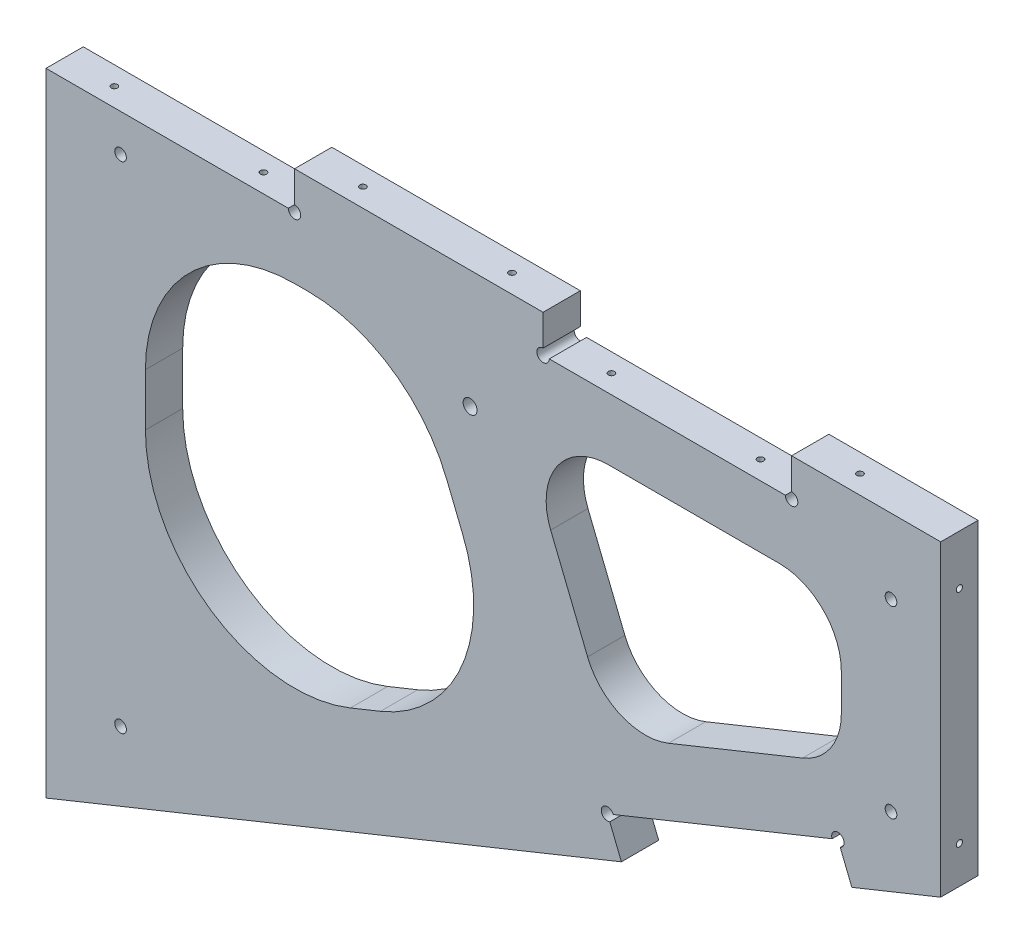
SolidWorks part; units mm, degrees
material "Beech"
ref_plane "Front Plane" through (0, 0, 0) normal (0, 0, 1) x (1, 0, 0)
ref_plane "Top Plane" through (0, 0, 0) normal (0, 1, 0) x (1, 0, 0)
ref_plane "Right Plane" through (0, 0, 0) normal (1, 0, 0) x (0, 0, -1)
sketch "Sketch1" plane through (0, 0, 0) normal (0, 0, 1) x (1, 0, 0)
  line L0 (3140.71, 6983.73) -> (2683.51, 6983.73)
  line L1 (3140.71, 6826.4627) -> (3140.71, 6983.73) construction
  line L2 (3140.71, 6983.73) -> (2683.51, 6983.73) construction
  line L3 (2683.51, 6983.73) -> (2683.51, 6641.7419)
  line L4 (2683.51, 6641.7419) -> (3140.71, 6826.4627)
  line L5 (3140.71, 6826.4627) -> (3140.71, 6983.73)
extrude "Boss-Extrude1" add sketch "Sketch1" along normal blind 19.05
sketch "Sketch6" plane through (0, 0, 0) normal (0, 0, -1) x (-1, 0, 0)
  line L0 (-2925.0567, 6794.1227) -> (-2872.8192, 6923.415) construction
  line L1 (-2923.7645, 6932.93) -> (-3089.91, 6932.93)
  line L2 (-2925.0567, 6794.1227) -> (-2734.31, 6717.056)
  line L4 (-2948.6072, 6803.6377) -> (-2896.3697, 6932.93) construction
  line L5 (-2925.0567, 6794.1227) -> (-2868.9749, 6932.93)
  line L6 (-2972.1577, 6813.1527) -> (-2923.7645, 6932.93)
  line L7 (-2972.1577, 6813.1527) -> (-2919.9202, 6942.445) construction
  line L8 (-3089.91, 6932.93) -> (-3089.91, 6860.7277)
  line L9 (-3089.91, 6860.7277) -> (-2734.31, 6717.056)
  line L10 (-2734.31, 6717.056) -> (-2734.31, 6932.93)
  line L11 (-2734.31, 6932.93) -> (-3089.91, 6932.93)
  line L12 (-3089.91, 6932.93) -> (-3089.91, 6860.7277)
  line L13 (-3089.91, 6860.7277) -> (-2972.1577, 6813.1527)
  line L14 (-2734.31, 6717.056) -> (-2734.31, 6932.93)
  line L15 (-2734.31, 6932.93) -> (-2868.9749, 6932.93)
  dimension "D2" = 152.4
  dimension "D1" = 50.8
  dimension "D3" = 25.4
  dimension "D4" = 25.4
extrude "Cut-Extrude2" cut sketch "Sketch6" against normal through all
fillet "Fillet1" radius 76.2 4 edges at (2734.31, 6932.93, 9.525) (2868.9749, 6932.93, 9.525) (2925.0567, 6794.1227, 9.525) (2734.31, 6717.056, 9.525)
fillet "Fillet2" radius 31.75 4 edges at (3089.91, 6860.7277, 9.525) (2972.1577, 6813.1527, 9.525) (2923.7645, 6932.93, 9.525) (3089.91, 6932.93, 9.525)
sketch "Sketch2" plane through (0, 0, 0) normal (0, 0, -1) x (-1, 0, 0)
  line L0 (-2683.51, 6964.68) -> (-2810.51, 6964.68) construction
  line L1 (-2810.51, 6964.68) -> (-2810.51, 6983.73) construction
  line L2 (-2810.51, 6983.73) -> (-2683.51, 6983.73) construction
  line L3 (-2683.51, 6983.73) -> (-2683.51, 6964.68) construction
  line L4 (-2937.51, 6964.68) -> (-3064.51, 6964.68) construction
  line L5 (-3064.51, 6964.68) -> (-3064.51, 6983.73) construction
  line L6 (-3064.51, 6983.73) -> (-2937.51, 6983.73) construction
  line L7 (-2937.51, 6983.73) -> (-2937.51, 6964.68) construction
  line L8 (-2977.5519, 6760.5425) -> (-3095.3042, 6808.1176) construction
  line L9 (-3095.3042, 6808.1176) -> (-3088.168, 6825.7804) construction
  line L10 (-3088.168, 6825.7804) -> (-2970.4156, 6778.2054) construction
  line L11 (-2970.4156, 6778.2054) -> (-2977.5519, 6760.5425) construction
  line L12 (-2683.51, 6964.68) -> (-2810.51, 6964.68)
  line L13 (-2810.51, 6964.68) -> (-2810.51, 6983.73)
  line L14 (-2810.51, 6983.73) -> (-2683.51, 6983.73)
  line L15 (-2683.51, 6983.73) -> (-2683.51, 6964.68)
  line L16 (-2937.51, 6964.68) -> (-3064.51, 6964.68)
  line L17 (-3064.51, 6964.68) -> (-3064.51, 6983.73)
  line L18 (-3064.51, 6983.73) -> (-2937.51, 6983.73)
  line L19 (-2937.51, 6983.73) -> (-2937.51, 6964.68)
  line L20 (-2977.5519, 6760.5425) -> (-3095.3042, 6808.1176)
  line L21 (-3095.3042, 6808.1176) -> (-3088.168, 6825.7804)
  line L22 (-3088.168, 6825.7804) -> (-2970.4156, 6778.2054)
  line L23 (-2970.4156, 6778.2054) -> (-2977.5519, 6760.5425)
extrude "Cut-Extrude1" cut sketch "Sketch2" against normal through all
hole_wizard "1/4 (0.25) Diameter Hole1" positions "Sketch3" profile "Sketch4" hole size "1/4" standard "ANSI Inch" end condition through all
sketch "Sketch3" plane through (0, 0, 0) normal (0, 0, -1) x (-1, 0, 0)
  point P0 (-3088.168, 6825.7804)
  point P3 (-2970.4156, 6778.2054)
  point P6 (-2937.51, 6964.68)
  point P9 (-3064.51, 6964.68)
  point P12 (-2810.51, 6964.68)
sketch "Sketch4" plane through (3088.168, 6825.7804, 0) normal (1, 0, 0) x (0, 1, 0)
  line L0 (0, 0) -> (0, 19.05)
  line L1 (0, 19.05) -> (3.175, 19.05)
  line L2 (3.175, 19.05) -> (3.175, 0)
  line L5 (3.175, 0) -> (0, 0)
  line L11 (0, -6.35) -> (0, 107.95) construction
  dimension "Thru Hole Dia." = 6.35
  dimension "Thru Hole Depth" = 19.05
hole_wizard "15/64 (0.23438) Diameter Hole1" positions "Sketch7" profile "Sketch8" hole size "15/64" standard "ANSI Inch" end condition through all
sketch "Sketch7" plane through (0, 0, 0) normal (0, 0, -1) x (0, 1, 0)
  point P0 (6692.5419, 2721.61)
  point P1 (6945.63, 2721.61)
  point P2 (6945.63, 3115.31)
  point P3 (6851.607, 3115.31)
sketch "Sketch8" plane through (2721.61, 6692.5419, 0) normal (1, 0, 0) x (0, 1, 0)
  line L0 (0, 0) -> (0, 19.05)
  line L1 (0, 19.05) -> (2.9766, 19.05)
  line L2 (2.9766, 19.05) -> (2.9766, 0)
  line L3 (2.9766, 0) -> (0, 0)
  line L4 (0, -6.35) -> (0, 107.95) construction
  dimension "Thru Hole Dia." = 5.9533
  dimension "Thru Hole Depth" = 19.05
hole_wizard "1/4 Clearance Hole1" positions "Sketch9" profile "Sketch10" hole size "1/4" standard "ANSI Inch" end condition through all
sketch "Sketch9" plane through (0, 0, 0) normal (0, 0, -1) x (-1, 0, 0)
  point P0 (-2900.218, 6923.405)
sketch "Sketch10" plane through (2900.218, 6923.405, 0) normal (1, 0, 0) x (0, 1, 0)
  line L0 (0, 0) -> (0, 19.05)
  line L1 (0, 19.05) -> (3.5712, 19.05)
  line L2 (3.5712, 19.05) -> (3.5712, 0)
  line L5 (3.5712, 0) -> (0, 0)
  line L11 (0, -6.35) -> (0, 107.95) construction
  dimension "Thru Hole Dia." = 7.1425
  dimension "Thru Hole Depth" = 19.05
hole_wizard "Hole1" positions "Sketch11" profile "Sketch12" legacy
sketch "Sketch11" plane through (0, 7002.78, 247.523) normal (0, 1, 0) x (0, 0, 1)
  line L0 (-237.998, 3140.71) -> (-237.998, 2683.51) construction
  line L9 (0, 3140.71) -> (0, 2683.51) construction
  point P13 (-237.998, 3089.91)
  point P15 (-237.998, 3039.11)
  point P17 (-237.998, 2962.91)
  point P19 (-237.998, 2912.11)
  point P21 (-237.998, 2835.91)
  point P23 (-237.998, 2785.11)
  point P25 (-237.998, 2708.91)
  point P38 (237.998, 2708.91)
  point P39 (237.998, 2785.11)
  point P40 (237.998, 2835.91)
  point P41 (237.998, 2912.11)
  point P42 (237.998, 2962.91)
  point P43 (237.998, 3039.11)
  point P44 (237.998, 3089.91)
  point P50 (0, 3051.81)
  point P52 (0, 2950.21)
  point P54 (0, 2797.81)
  point P56 (0, 2696.21)
sketch "Sketch12" plane through (2696.21, 7002.78, 247.523) normal (1, 0, 0) x (0, 0, 1)
  line L0 (0, 0) -> (0, 51.7539)
  line L1 (0, 51.7539) -> (1.5875, 50.8)
  line L2 (1.5875, 50.8) -> (1.5875, 4.0177)
  line L3 (1.5875, 4.0177) -> (5.08, 0)
  line L4 (5.08, 0) -> (0, 0)
  line L5 (0, -14.3089) -> (0, 102.4216) construction
  line L6 (0, 51.7539) -> (-1.5875, 50.8) construction
  line L7 (-1.5875, 4.0177) -> (-5.08, 0) construction
  dimension "Diameter" = 3.175
  dimension "Depth" = 50.8
  dimension "C-Sink Diameter" = 10.16
  dimension "C-Sink Angle" = 82
  dimension "Drill Angle" = 118
hole_wizard "Hole2" positions "Sketch13" profile "Sketch14" legacy
sketch "Sketch13" plane through (3159.76, 0, 247.523) normal (1, 0, 0) x (0, 0, -1)
  line L0 (237.998, 6813.6133) -> (237.998, 7002.78) construction
  line L5 (0, 6813.6133) -> (0, 7002.78) construction
  line L7 (266.573, 6993.255) -> (-266.573, 6993.255) construction
  line L17 (237.998, 6845.5127) -> (237.998, 6958.33)
  line L18 (237.998, 6993.255) -> (0, 6993.255)
  point P30 (237.998, 6993.255)
  point P32 (237.998, 6958.33)
  point P34 (237.998, 6845.5127)
  point P50 (-237.998, 6993.255)
  point P51 (-237.998, 6958.33)
  point P52 (-237.998, 6845.5127)
  point P60 (118.999, 6993.255)
  point P64 (-118.999, 6993.255)
sketch "Sketch14" plane through (3159.76, 6993.255, 366.522) normal (0, 1, 0) x (0, 0, -1)
  line L0 (0, 0) -> (0, 39.0539)
  line L1 (0, 39.0539) -> (1.5875, 38.1)
  line L2 (1.5875, 38.1) -> (1.5875, 4.0177)
  line L3 (1.5875, 4.0177) -> (5.08, 0)
  line L4 (5.08, 0) -> (0, 0)
  line L5 (0, -14.3089) -> (0, 102.4216) construction
  line L6 (0, 39.0539) -> (-1.5875, 38.1) construction
  line L7 (-1.5875, 4.0177) -> (-5.08, 0) construction
  dimension "Diameter" = 3.175
  dimension "Depth" = 38.1
  dimension "C-Sink Diameter" = 10.16
  dimension "C-Sink Angle" = 82
  dimension "Drill Angle" = 118
hole_wizard "Hole3" positions "Sketch15" profile "Sketch16" legacy
sketch "Sketch15" plane through (-1923.1573, 4759.9814, 247.523) normal (0.3746, -0.9272, 0) x (0, 0, -1)
  line L0 (-237.998, 5461.5568) -> (-237.998, 4968.4508) construction
  line L6 (0, 5461.5568) -> (0, 5275.5865) construction
  line L10 (-237.998, 5267.8818) -> (-237.998, 4993.8508)
  point P19 (-237.998, 5442.5068)
  point P21 (-237.998, 5394.8818)
  point P23 (-237.998, 5318.6818)
  point P32 (0, 5407.5818)
  point P34 (0, 5305.9818)
  point P37 (-237.998, 5267.8818)
  point P39 (-237.998, 5130.8663)
  point P41 (-237.998, 4993.8508)
  point P64 (237.998, 4993.8508)
  point P65 (237.998, 5130.8663)
  point P66 (237.998, 5267.8818)
  point P67 (237.998, 5318.6818)
  point P68 (237.998, 5394.8818)
  point P69 (237.998, 5442.5068)
sketch "Sketch16" plane through (3123.0471, 6798.7803, 9.525) normal (0, 0, 1) x (0.9272, 0.3746, 0)
  line L0 (0, 0) -> (0, 51.7539)
  line L1 (0, 51.7539) -> (1.5875, 50.8)
  line L2 (1.5875, 50.8) -> (1.5875, 4.0177)
  line L3 (1.5875, 4.0177) -> (5.08, 0)
  line L4 (5.08, 0) -> (0, 0)
  line L5 (0, -14.3089) -> (0, 102.4216) construction
  line L6 (0, 51.7539) -> (-1.5875, 50.8) construction
  line L7 (-1.5875, 4.0177) -> (-5.08, 0) construction
  dimension "Diameter" = 3.175
  dimension "Depth" = 50.8
  dimension "C-Sink Diameter" = 10.16
  dimension "C-Sink Angle" = 82
  dimension "Drill Angle" = 118
hole_wizard "Hole4" positions "Sketch17" profile "Sketch18" legacy
sketch "Sketch17" plane through (2664.46, 0, 247.523) normal (-1, 0, 0) x (0, 0, 1)
  line L0 (0, 7002.78) -> (0, 5935.98) construction
  line L4 (237.998, 7002.78) -> (237.998, 5935.98) construction
  line L8 (266.573, 6993.255) -> (0, 6993.255) construction
  line L12 (237.998, 6939.28) -> (237.998, 6686.1919)
  point P26 (237.998, 6686.1919)
  point P27 (257.048, 6993.255)
  point P29 (218.948, 6993.255)
  point P31 (19.05, 6993.255)
  point P35 (237.998, 6939.28)
  point P42 (237.998, 6812.7359)
  point P51 (-237.998, 6812.7359)
  point P52 (-237.998, 6939.28)
  point P53 (-19.05, 6993.255)
  point P54 (-218.948, 6993.255)
  point P55 (-257.048, 6993.255)
  point P56 (-237.998, 6686.1919)
sketch "Sketch18" plane through (2664.46, 6686.1919, 9.525) normal (0, 1, 0) x (0, 0, 1)
  line L0 (0, 0) -> (0, 39.0539)
  line L1 (0, 39.0539) -> (1.5875, 38.1)
  line L2 (1.5875, 38.1) -> (1.5875, 4.0177)
  line L3 (1.5875, 4.0177) -> (5.08, 0)
  line L4 (5.08, 0) -> (0, 0)
  line L5 (0, -14.3089) -> (0, 102.4216) construction
  line L6 (0, 39.0539) -> (-1.5875, 38.1) construction
  line L7 (-1.5875, 4.0177) -> (-5.08, 0) construction
  dimension "Diameter" = 3.175
  dimension "Depth" = 38.1
  dimension "C-Sink Diameter" = 10.16
  dimension "C-Sink Angle" = 82
  dimension "Drill Angle" = 118
